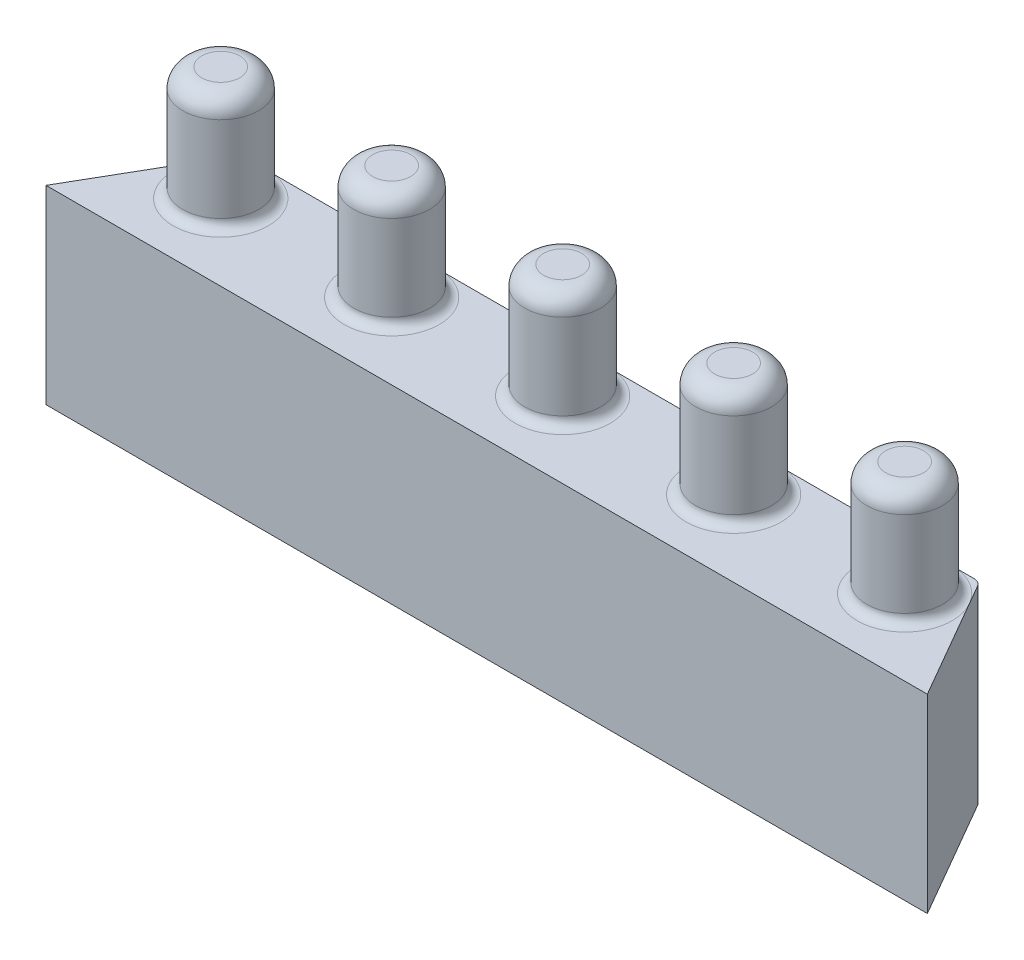
SolidWorks part; units mm, degrees
ref_plane "Front Plane" through (0, 0, 0) normal (0, 0, 1) x (1, 0, 0)
ref_plane "Top Plane" through (0, 0, 0) normal (0, 1, 0) x (1, 0, 0)
ref_plane "Right Plane" through (0, 0, 0) normal (1, 0, 0) x (0, 0, -1)
sketch "Sketch1" plane through (0, 0, 0) normal (0, 1, 0) x (1, 0, 0)
  line L0 (0, 0) -> (9, 0) construction
  line L1 (-1.4434, 2.5) -> (37.4434, 2.5)
  line L2 (18, 2.5) -> (18, 0) construction
  line L3 (-1.4434, 2.5) -> (-5.1962, -4)
  line L4 (-5.1962, -4) -> (41.1962, -4)
  line L5 (37.4434, 2.5) -> (41.1962, -4)
  circle A0 centre (0, 0) radius 2
  circle A1 centre (9, 0) radius 2
  circle A2 centre (18, 0) radius 2
  circle A3 centre (27, 0) radius 2
  circle A4 centre (36, 0) radius 2
  point P19 (18, -4)
  dimension "D1" = 4
  dimension "D5" = 120
  dimension "D6" = 2.5
  dimension "D7" = 4
  dimension "D3" = 9
  dimension "D4" = 2.5
  dimension "D2" = 5
extrude "Boss-Extrude1" add sketch "Sketch1" along normal blind 10
extrude "Boss-Extrude2" add sketch "Sketch1<2>" along normal blind 16 contours A0 | A1 | A2 | A3 | A4 region at (0, 0, 0) region at (9, 0, 0) region at (18, 0, 0) region at (27, 0, 0) region at (36, 0, 0)
sketch "Sketch1<2>" plane through (0, 0, 0) normal (0, 1, 0) x (1, 0, 0) same geometry as "Sketch1"
fillet "Fillet1" radius 1 5 edges at (0, 16, 2) (9, 16, 2) (18, 16, 2) (27, 16, 2) (36, 16, 2)
fillet "Fillet2" radius 0.5 7 edges at (-1.4434, 5, -2.5) (37.4434, 5, -2.5) (36, 10, 2) (27, 10, 2) (18, 10, 2) (9, 10, 2) (0, 10, 2)
